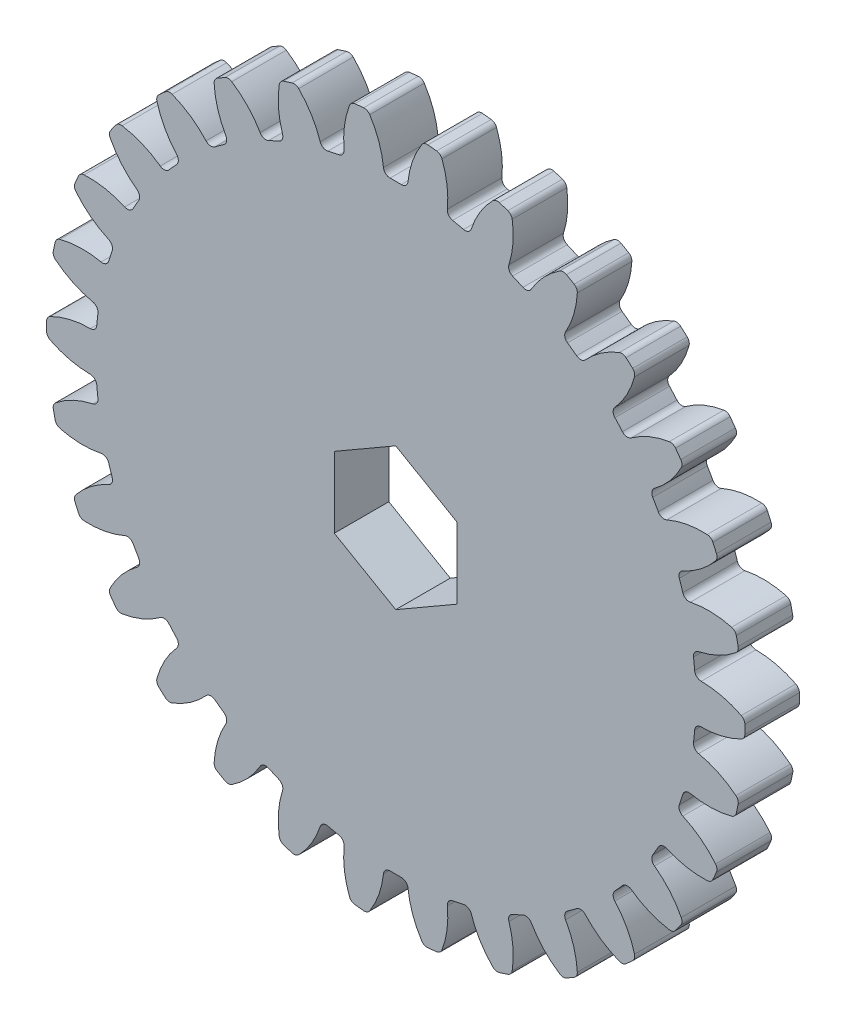
SolidWorks part; units mm, degrees
other "Markup1"
sketch "Sketch17" plane through (-10.9062, 10.9062, 11.3) normal (-0.0184, 0.3965, 0.9179) x (0.5503, 0.7705, -0.3218)
ref_plane "Front Plane" through (0, 0, 0) normal (0, 0, 1) x (1, 0, 0)
ref_plane "Top Plane" through (0, 0, 0) normal (0, 1, 0) x (1, 0, 0)
ref_plane "Right Plane" through (0, 0, 0) normal (1, 0, 0) x (0, 0, -1)
sketch "Sketch1" plane through (0, 0, 0) normal (0, 0, 1) x (1, 0, 0)
  circle A2 centre (0, 0) radius 30
  circle A3 centre (0, 0) radius 32
  circle A4 centre (0, 0) radius 27.5
  dimension "D1" = 60
  dimension "D2" = 64
  dimension "D3" = 4.5
extrude "Boss-Extrude1" add sketch "Sketch1" along normal mid plane 5 contours A3
sketch "Sketch3" plane through (0, 0, 2.5) normal (0, 0, 1) x (1, 0, 0)
  line L0 (0, 0) -> (0, 32) construction
  line L1 (-1.5701, 29.9589) -> (1.5701, 29.9589) construction
  line L2 (0, 0) -> (-1.0822, 27.4787) construction
  line L3 (0, 25.6451) -> (-2.6385, 32.8944) construction
  line L4 (0, 0) -> (3.3449, 31.8247) construction
  line L5 (1.5701, 29.9589) -> (4.693, 29.6307) construction
  circle A0 centre (0, 0) radius 32 construction
  arc A1 (-3.3568, 32.8288) -> (-1.0822, 27.4787) centre (-9.2704, 27.1562) cw
  arc A2 (3.3568, 32.8288) -> (1.0822, 27.4787) centre (9.2704, 27.1562) ccw
  circle A3 centre (0, 0) radius 27.5 construction
  arc A4 (1.0822, 27.4787) -> (-1.0822, 27.4787) centre (0, 0) ccw
  circle A5 centre (0, 0) radius 30 construction
  circle A6 centre (0, 0) radius 32 construction
  circle A7 centre (0, 0) radius 33
  arc A8 (3.3568, 32.8288) -> (-3.3568, 32.8288) centre (0, 0) ccw
  dimension "D2" = 20
  dimension "D3" = 6
extrude "Cut-Extrude1" cut sketch "Sketch3" against normal through all both and the other way through all
fillet "Fillet1" radius 0.6 4 edges at (1.0822, 27.4787, 0) (-1.0822, 27.4787, 0) (2.5853, 31.8954, 0) (-2.5853, 31.8954, 0)
pattern_circular "CirPattern1" count 30 over 360 about axis through (0, 0, 2.5) along (0, 0, -1) of "Cut-Extrude1", "Fillet1"
sketch "Sketch23" plane through (0, 0, -2.5) normal (0, 0, -1) x (-1, 0, 0)
  circle A0 centre (0, 0) radius 3.25
extrude "Cut-Extrude9" cut sketch "Sketch23" against normal blind 0.7
sketch "Sketch24" plane through (0, 0, 2.5) normal (0, 0, 1) x (1, 0, 0)
  circle A0 centre (0, 0) radius 4
  dimension "D1" = 8
extrude "Cut-Extrude10" cut sketch "Sketch24" against normal blind 10
sketch "Sketch25" plane through (0, 0, 2.5) normal (0, 0, 1) x (1, 0, 0)
  circle A0 centre (0, 0) radius 4.6038
extrude "Boss-Extrude2" add sketch "Sketch25" against normal through all
sketch "Sketch26" plane through (0, 0, -2.5) normal (0, 0, -1) x (-1, 0, 0)
  circle A0 centre (0, 0) radius 2.8
  dimension "D1" = 5.6
extrude "Cut-Extrude11" cut sketch "Sketch26" against normal blind 10
sketch "Sketch27" plane through (0, 0, -2.5) normal (0, 0, -1) x (-1, 0, 0)
  line L1 (0, 6.5) -> (-5.6292, 3.25)
  line L2 (-5.6292, 3.25) -> (-5.6292, -3.25)
  line L3 (-5.6292, -3.25) -> (0, -6.5)
  line L4 (0, -6.5) -> (5.6292, -3.25)
  line L5 (5.6292, -3.25) -> (5.6292, 3.25)
  line L6 (5.6292, 3.25) -> (0, 6.5)
  circle A0 centre (0, 0) radius 5.6292 construction
  dimension "D1" = 13
extrude "Cut-Extrude12" cut sketch "Sketch27" against normal blind 10
equation "\"Module\"= 2mm"
equation "\"Number of Teeth\"= 30"
equation "\"D1@Sketch1\"=\"Module\" * \"Number of Teeth\""
equation "\"D2@Sketch1\"=(\"Number of Teeth\" + 2) * \"Module\""
equation "\"D3@Sketch1\"=\"Module\" * if( \"Module\"=>1.25,2.25,2.4)"
equation "\"D3@Sketch3\"=180 / \"Number of Teeth\""
equation "\"D1@Fillet1\"=0.3 * \"Module\""
equation "\"D1@CirPattern1\"=\"Number of Teeth\""
